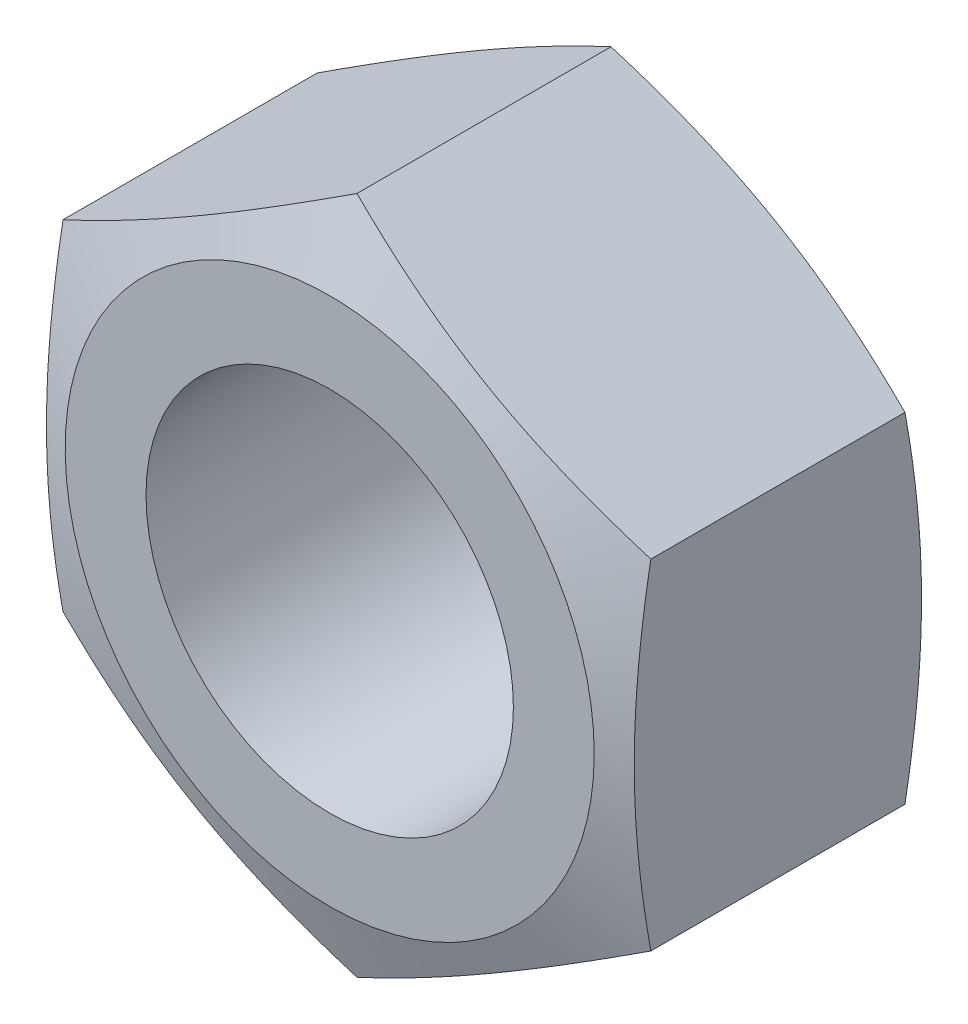
SolidWorks part; units mm, degrees
ref_plane "前视基准面" through (0, 0, 0) normal (0, 0, 1) x (1, 0, 0)
ref_plane "上视基准面" through (0, 0, 0) normal (0, 1, 0) x (1, 0, 0)
ref_plane "右视基准面" through (0, 0, 0) normal (1, 0, 0) x (0, 0, -1)
sketch "草图1" plane through (0, 0, 0) normal (0, 0, 1) x (1, 0, 0)
  line L1 (0, 9.2376) -> (-8, 4.6188)
  line L2 (-8, 4.6188) -> (-8, -4.6188)
  line L3 (-8, -4.6188) -> (0, -9.2376)
  line L4 (0, -9.2376) -> (8, -4.6188)
  line L5 (8, -4.6188) -> (8, 4.6188)
  line L6 (8, 4.6188) -> (0, 9.2376)
  circle A0 centre (0, 0) radius 8 construction
  dimension "s" = 16
extrude "凸台-拉伸1" add sketch "草图1" along normal blind 8.4
sketch "草图4" plane through (0, 0, 0) normal (1, 0, 0) x (0, 0, -1)
  line L0 (-8.4, -7.2) -> (-7.6584, -9.2376)
  line L1 (-8.4, -4.6188) -> (-8.4, -9.2376) construction
  line L2 (-8.4, -9.2376) -> (0, -9.2376) construction
  line L3 (-7.6584, -9.2376) -> (-8.4, -9.2376)
  line L4 (-8.4, -9.2376) -> (-8.4, -7.2)
  line L5 (-8.4, 0) -> (0, 0) construction
  line L6 (-8.4, 4.6188) -> (-8.4, -4.6188) construction
  line L7 (0, 4.6188) -> (0, -4.6188) construction
  dimension "D1" = 20
  dimension "D2" = 7.2
revolve "切除-旋转1" cut sketch "草图4" angle 360 about L5
ref_plane "基准面1" through (0, 0, 4.2) normal (0, 0, 1) x (1, 0, 0)
mirror "镜向1" about plane through (0, 0, 4.2) normal (0, 0, 1) of "切除-旋转1"
sketch "草图5" plane through (0, 0, 8.4) normal (0, 0, 1) x (1, 0, 0)
  circle A0 centre (0, 0) radius 5
  dimension "D1" = 10
extrude "切除-拉伸1" cut sketch "草图5" against normal through all
ref_axis "基准轴1" through (0, 0, 0) along (0, 0, 1)
ref_plane "基准面2" through (0, 0, 0) normal (0, 0, -1) x (-1, 0, 0)
ref_plane "基准面3" through (0, 0, 8.4) normal (0, 0, 1) x (1, 0, 0)
equation "\"D2@草图4\"= \"s@草图1\" * 0.45"
